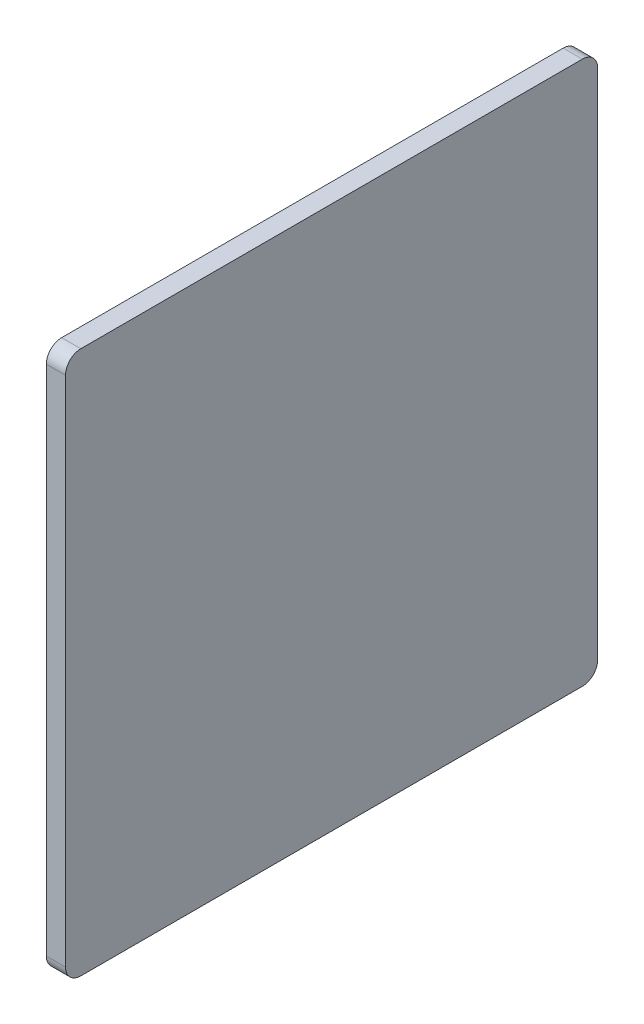
SolidWorks part; units mm, degrees
material "Acrylic (Medium-high impact)"
ref_plane "Front Plane" through (0, 0, 0) normal (0, 0, 1) x (1, 0, 0)
ref_plane "Top Plane" through (0, 0, 0) normal (0, 1, 0) x (1, 0, 0)
ref_plane "Right Plane" through (0, 0, 0) normal (1, 0, 0) x (0, 0, -1)
sketch "Sketch1" plane through (0, 0, 0) normal (1, 0, 0) x (0, 0, -1)
  line L1 (44.0875, -45) -> (-44.0875, -45)
  line L2 (44.0875, -45) -> (44.0875, 45)
  line L3 (44.0875, 45) -> (-44.0875, 45)
  line L4 (-44.0875, -45) -> (-44.0875, 45)
  line L5 (44.0875, -45) -> (-44.0875, 45) construction
  line L6 (44.0875, 45) -> (-44.0875, -45) construction
  point P0 (0, 0)
  dimension "D1" = 88.175
  dimension "D2" = 90
extrude "Boss-Extrude1" add sketch "Sketch1" along normal blind 3.175
fillet "Fillet1" radius 2.54 4 edges at (1.5875, -45, 44.0875) (1.5875, -45, -44.0875) (1.5875, 45, -44.0875) (1.5875, 45, 44.0875)
